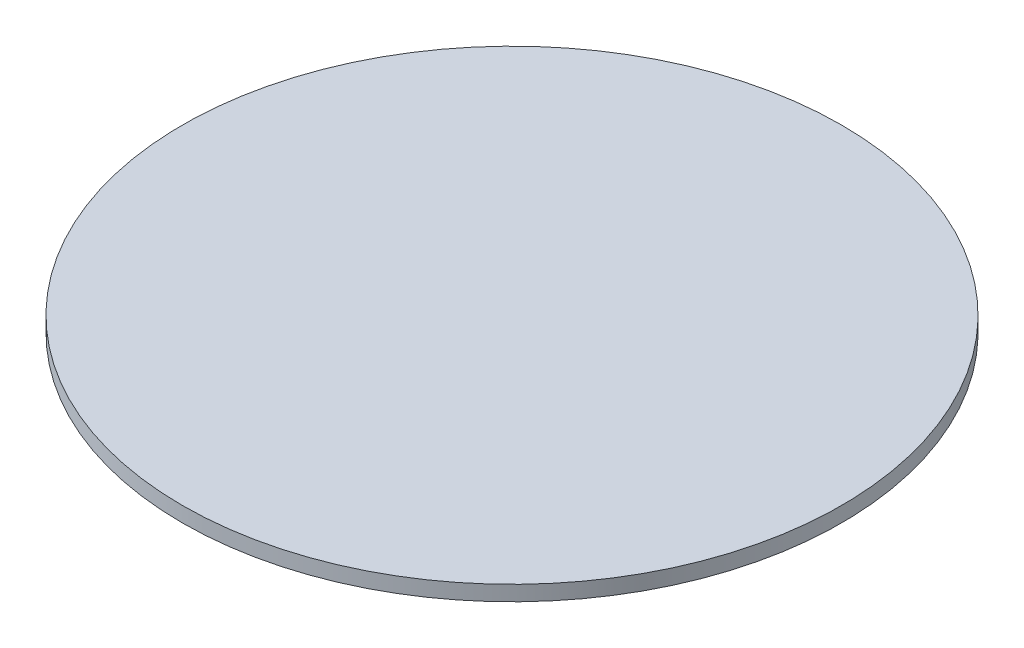
SolidWorks part; units mm, degrees
ref_plane "Front Plane" through (0, 0, 0) normal (0, 0, 1) x (1, 0, 0)
ref_plane "Top Plane" through (0, 0, 0) normal (0, 1, 0) x (1, 0, 0)
ref_plane "Right Plane" through (0, 0, 0) normal (1, 0, 0) x (0, 0, -1)
sketch "Sketch1" plane through (0, 0, 0) normal (0, 1, 0) x (1, 0, 0)
  line L1 (-3.45, -3.45) -> (26.55, -3.45)
  line L2 (-3.45, -3.45) -> (-3.45, 3.45)
  line L3 (-3.45, 3.45) -> (26.55, 3.45)
  line L4 (26.55, -3.45) -> (26.55, 3.45)
  line L5 (-1.15, -1.15) -> (1.15, -1.15)
  line L6 (-1.15, -1.15) -> (-1.15, 1.15)
  line L7 (-1.15, 1.15) -> (1.15, 1.15)
  line L8 (1.15, -1.15) -> (1.15, 1.15)
  line L9 (-1.15, -1.15) -> (1.15, 1.15) construction
  line L10 (-1.15, 1.15) -> (1.15, -1.15) construction
  point P4 (0, 0)
  dimension "D1" = 6.9
  dimension "D2" = 30
  dimension "D3" = 2.3
  dimension "D4" = 2.3
  dimension "D5" = 2.3
  dimension "D6" = 2.3
base flange "Base-Flange1" sketch "Sketch1" thickness 2.3 reverse thickness direction no parameters "D1"=0.7366
sketch "Sketch6" plane through (0, 0, 0) normal (0, 1, 0) x (1, 0, 0)
  line L1 (0, 13.4455) -> (2.3, 13.4455)
  line L2 (2.3, 13.4455) -> (2.3, 11.1455)
  line L3 (2.3, 11.1455) -> (6.9, 11.1455)
  line L4 (6.9, 11.1455) -> (6.9, 11.3955)
  line L5 (6.9, 11.3955) -> (7.6562, 11.2311)
  line L6 (8.05, 10.7425) -> (8.05, 10.2455)
  line L7 (8.05, 10.2455) -> (4.6, 9.9955)
  line L15 (4.1743, 9.9955) -> (13.3059, 9.9955) construction
  line L16 (0, 13.4455) -> (0, 6.5455)
  line L17 (8.05, 9.7455) -> (4.6, 9.9955)
  line L18 (8.05, 9.2484) -> (8.05, 9.7455)
  line L19 (6.9, 8.5955) -> (7.6562, 8.7599)
  line L20 (6.9, 8.8455) -> (6.9, 8.5955)
  line L21 (2.3, 8.8455) -> (6.9, 8.8455)
  line L22 (2.3, 6.5455) -> (2.3, 8.8455)
  line L23 (0, 6.5455) -> (2.3, 6.5455)
  arc A0 (7.6562, 11.2311) -> (8.05, 10.7425) centre (7.55, 10.7425) cw
  arc A1 (7.6562, 8.7599) -> (8.05, 9.2484) centre (7.55, 9.2484) ccw
  point P14 (8.05, 11.1455)
  point P21 (0, 9.9955)
  point P26 (8.05, 8.8455)
  dimension "D8" = 0.5
  dimension "D1" = 2.3
  dimension "D2" = 2.3
  dimension "D3" = 1.15
  dimension "D4" = 4.6
  dimension "D5" = 0.25
  dimension "D6" = 0.25
  dimension "D7" = 1.15
  dimension "D9" = 4.6
base flange "Base-Flange2" sketch "Sketch6" thickness 2.3 reverse thickness direction no parameters "D1"=0.7366
sketch "Sketch9" plane through (0, 0, 0) normal (0, 1, 0) x (1, 0, 0)
  circle A0 centre (16.0143, 23.6912) radius 12.5
  circle A1 centre (16.0143, 23.6912) radius 1.5
  dimension "D1" = 25
  dimension "D2" = 3
base flange "Base-Flange3" sketch "Sketch9" thickness 2.3 reverse thickness direction no parameters "D1"=0.7366
sketch "Sketch10" plane through (0, 0, 0) normal (0, 1, 0) x (1, 0, 0)
  circle A0 centre (0, 0) radius 50
  dimension "D1" = 100
base flange "Base-Flange4" sketch "Sketch10" thickness 2.3 reverse thickness direction no parameters "D1"=0.7366
sketch "Bend-Lines1" [suppressed] plane through (0, 0, 0) normal (0, 1, 0) x (1, 0, 0)
sketch "Bounding-Box1" [suppressed] plane through (0, 0, 0) normal (0, 1, 0) x (1, 0, 0)
sheet metal parameters "Sheet-Metal1" thickness 2.3 parameters "D1"=0.7366
flat pattern "Flat-Pattern1" [suppressed]
sketch "Bend-Lines2" plane through (0, 0, 0) normal (0, 1, 0) x (1, 0, 0)
sketch3d "Bounding-Box2" [suppressed]
  line L0 (26.55, 3.45, 0) -> (-3.45, 3.45, 0) construction
  line L1 (26.55, -3.45, 0) -> (-3.45, -3.45, 0) construction
  line L2 (26.55, 3.45, 0) -> (26.55, -3.45, 0) construction
  line L3 (-3.45, 3.45, 0) -> (-3.45, -3.45, 0) construction
sheet metal parameters "Sheet-Metal2" thickness 2.3 parameters "D1"=0.7366
flat pattern "Flat-Pattern2"
sketch "Bend-Lines3" plane through (0, 0, 0) normal (0, 1, 0) x (1, 0, 0)
sketch3d "Bounding-Box3" [suppressed]
  line L0 (0.5, -2.703, 0) -> (-7.55, -2.703, 0) construction
  line L1 (0.5, 4.197, 0) -> (-7.55, 4.197, 0) construction
  line L2 (0.5, -2.703, 0) -> (0.5, 4.197, 0) construction
  line L3 (-7.55, -2.703, 0) -> (-7.55, 4.197, 0) construction
sheet metal parameters "Sheet-Metal3" thickness 2.3 parameters "D1"=0.7366
flat pattern "Flat-Pattern3"
sketch "Bend-Lines4" plane through (0, 0, 0) normal (0, 1, 0) x (1, 0, 0)
sketch3d "Bounding-Box4" [suppressed]
  line L0 (-12.5451, 12.4546, 0) -> (-12.4545, -12.5451, 0) construction
  line L1 (12.4546, 12.5452, 0) -> (12.5452, -12.4545, 0) construction
  line L2 (-12.5451, 12.4546, 0) -> (12.4546, 12.5452, 0) construction
  line L3 (-12.4545, -12.5451, 0) -> (12.5452, -12.4545, 0) construction
sheet metal parameters "Sheet-Metal4" thickness 2.3 parameters "D1"=0.7366
flat pattern "Flat-Pattern4"
sketch "Bend-Lines5" plane through (0, 0, 0) normal (0, 1, 0) x (1, 0, 0)
sketch3d "Bounding-Box5" [suppressed]
  line L0 (-50.0306, 49.9694, 0) -> (-49.9694, -50.0306, 0) construction
  line L1 (49.9694, 50.0306, 0) -> (50.0306, -49.9694, 0) construction
  line L2 (-50.0306, 49.9694, 0) -> (49.9694, 50.0306, 0) construction
  line L3 (-49.9694, -50.0306, 0) -> (50.0306, -49.9694, 0) construction
